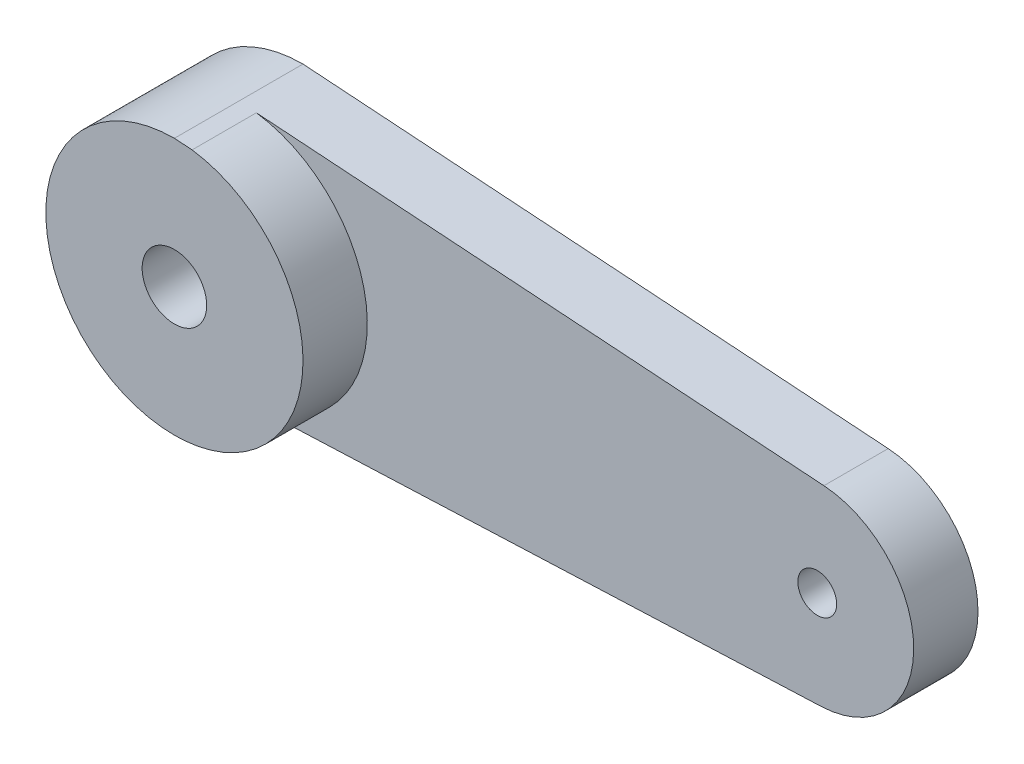
SolidWorks part; units mm, degrees
ref_plane "Front Plane" through (0, 0, 0) normal (0, 0, 1) x (1, 0, 0)
ref_plane "Top Plane" through (0, 0, 0) normal (0, 1, 0) x (1, 0, 0)
ref_plane "Right Plane" through (0, 0, 0) normal (1, 0, 0) x (0, 0, -1)
sketch "Sketch1" plane through (0, 0, 0) normal (0, 0, 1) x (1, 0, 0)
  line L0 (0, 10) -> (45.5121, 6.8586)
  line L1 (0, -10) -> (45.3071, -8.1171)
  circle A0 centre (0, 0) radius 10
  circle A1 centre (44.9957, -0.6236) radius 7.5
  circle A2 centre (0, 0) radius 2.51
  circle A3 centre (44.9957, -0.6236) radius 1.51
  dimension "D2" = 20
  dimension "D3" = 15
  dimension "D4" = 5.02
  dimension "D5" = 3.02
  dimension "D1" = 45
extrude "Boss-Extrude1" add sketch "Sketch1" along normal blind 10 contours L0 A0 L1 A2 region at (0.6675, 9.6704, 0)
extrude "Boss-Extrude2" add sketch "Sketch1<3>" along normal blind 5 contours A1 L0 A0 L1 | A1 A3 region at (23.0889, -0.3255, 0) region at (50.3235, 4.3492, 0)
sketch "Sketch1<3>" plane through (0, 0, 0) normal (0, 0, 1) x (1, 0, 0) same geometry as "Sketch1"
